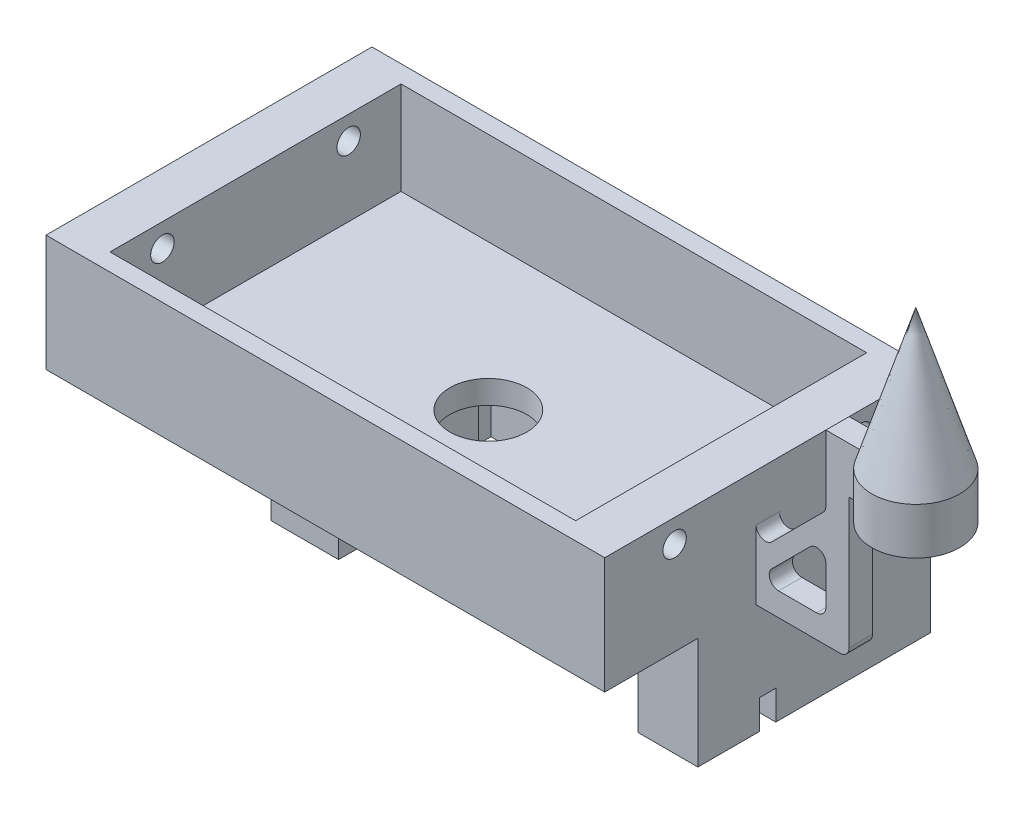
SolidWorks part; units mm, degrees
other "Markup1"
sketch "Sketch8" plane through (63.5, 15.875, 0) normal (0.0601, 0.2478, 0.9669) x (0.9981, -0.001, -0.0618)
ref_plane "Front Plane" through (0, 0, 0) normal (0, 0, 1) x (1, 0, 0)
ref_plane "Top Plane" through (0, 0, 0) normal (0, 1, 0) x (1, 0, 0)
ref_plane "Right Plane" through (0, 0, 0) normal (1, 0, 0) x (0, 0, -1)
sketch "Sketch1" plane through (0, 0, 0) normal (0, 1, 0) x (1, 0, 0)
  line L1 (0, 0) -> (63.5, 0)
  line L2 (0, 0) -> (0, 38.1)
  line L3 (0, 38.1) -> (63.5, 38.1)
  line L4 (63.5, 0) -> (63.5, 38.1)
  dimension "D1" = 38.1
  dimension "D2" = 63.5
extrude "Base" add sketch "Sketch1" along normal blind 3.175
sketch "Sketch3" plane through (0, 0, 0) normal (0, 1, 0) x (1, 0, 0)
  line L0 (0, 0) -> (63.5, 0) construction
  line L1 (0, 38.1) -> (-6.35, 38.1)
  line L2 (0, 38.1) -> (0, 0)
  line L3 (0, 0) -> (-6.35, 0)
  line L4 (-6.35, 38.1) -> (-6.35, 0)
  line L5 (63.5, 38.1) -> (69.85, 38.1)
  line L6 (63.5, 38.1) -> (63.5, 0)
  line L7 (63.5, 0) -> (69.85, 0)
  line L8 (69.85, 38.1) -> (69.85, 0)
  dimension "D1" = 6.35
extrude "Rod Holder" add sketch "Sketch3" along normal blind 15.875
sketch "Sketch4" plane through (69.85, 0, 0) normal (1, 0, 0) x (0, 0, -1)
  line L0 (0, 12.7) -> (38.1, 12.7) construction
  line L1 (0, 15.875) -> (0, 0) construction
  line L2 (38.1, 15.875) -> (38.1, 0) construction
  line L4 (38.1, 3.175) -> (0, 3.175) construction
  line L5 (0, 9.525) -> (38.1, 9.525) construction
  line L6 (11.595, 15.875) -> (11.595, 12.7) construction
  line L7 (0, 15.875) -> (38.1, 15.875) construction
  line L8 (11.595, 12.7) -> (11.595, 9.525) construction
  circle A0 centre (6.35, 12.7) radius 1.6
  circle A1 centre (31.75, 12.7) radius 1.6
  dimension "D1" = 3.2
  dimension "D3" = 6.35
  dimension "D2" = 6.35
  dimension "D4" = 6.35
extrude "Rod Hole" cut sketch "Sketch4" against normal through all
sketch "Sketch7" plane through (0, 3.175, 0) normal (0, 1, 0) x (1, 0, 0)
  line L0 (31.75, 38.1) -> (31.75, 0) construction
  line L1 (63.5, 38.1) -> (0, 38.1) construction
  line L2 (0, 0) -> (63.5, 0) construction
  circle A0 centre (31.75, 19.05) radius 5.25
  dimension "D1" = 10.5
extrude "GearPinHole_10.5mm" cut sketch "Sketch7" against normal through all
sketch "Sketch9" plane through (0, 0, 0) normal (0, -1, 0) x (1, 0, 0)
  line L1 (-6.35, 0) -> (69.85, 0)
  line L2 (-6.35, 0) -> (-6.35, 3.175)
  line L3 (-6.35, 3.175) -> (69.85, 3.175)
  line L4 (69.85, 0) -> (69.85, 3.175)
  line L5 (-6.35, -38.1) -> (69.85, -38.1)
  line L6 (-6.35, -38.1) -> (-6.35, -41.275)
  line L7 (-6.35, -41.275) -> (69.85, -41.275)
  line L8 (69.85, -38.1) -> (69.85, -41.275)
  dimension "D1" = 3.175
extrude "Boss-Extrude1" add sketch "Sketch9" against normal up to surface (15.875 mm away) up to face at (-3.175, 15.875, -19.05)
sketch "Sketch11" plane through (0, 0, 0) normal (0, -1, 0) x (1, 0, 0)
  line L0 (69.85, 3.175) -> (69.85, -41.275) construction
  line L1 (11.6546, -9.525) -> (19.85, -9.525)
  line L2 (11.6546, -9.525) -> (11.6546, -28.575)
  line L3 (11.6546, -28.575) -> (19.85, -28.575)
  line L4 (19.85, -9.525) -> (19.85, -28.575)
  line L5 (61.6546, -9.525) -> (69.85, -9.525)
  line L6 (61.6546, -9.525) -> (61.6546, -28.575)
  line L7 (61.6546, -28.575) -> (69.85, -28.575)
  line L8 (69.85, -9.525) -> (69.85, -28.575)
  point P14 (69.85, -19.05)
  point P15 (69.85, -19.05)
  dimension "D1" = 19.05
  dimension "D2" = 8.1954
extrude "Boss-Extrude2" add sketch "Sketch11" along normal blind 15.2
sketch "Sketch20" plane through (0, 0, 0) normal (0, -1, 0) x (1, 0, 0)
  line L1 (19.85, -9.525) -> (20.85, -9.525)
  line L2 (19.85, -9.525) -> (19.85, -28.575)
  line L3 (19.85, -28.575) -> (20.85, -28.575)
  line L4 (20.85, -9.525) -> (20.85, -28.575)
  dimension "D1" = 1
extrude "Boss-Extrude7" add sketch "Sketch20" along normal up to surface (15.2 mm away) up to face at (15.7523, -15.2, -19.05)
sketch "Sketch12" plane through (0, -15.2, 0) normal (0, -1, 0) x (1, 0, 0)
  line L2 (17.7523, -14.05) -> (20.85, -14.05) construction
  line L3 (20.85, -28.575) -> (20.85, -9.525) construction
  circle A0 centre (17.7523, -14.05) radius 1.5
  circle A1 centre (17.7523, -24.05) radius 1.5
  circle A2 centre (65.7523, -24.05) radius 1.5
  circle A3 centre (65.7523, -14.05) radius 1.5
  dimension "D1" = 3
  dimension "D2" = 3.0977
extrude "Cut-Extrude1" cut sketch "Sketch12" against normal blind 8.89
sketch "Sketch13" plane through (0, 0, 0) normal (0, -1, 0) x (1, 0, 0)
  line L1 (11.6546, -28.575) -> (16.7346, -28.575)
  line L2 (11.6546, -28.575) -> (11.6546, -41.275)
  line L4 (16.7346, -28.575) -> (16.7346, -34.417)
  line L5 (-6.35, -41.275) -> (69.85, -41.275) construction
  line L6 (69.85, -28.575) -> (64.77, -28.575)
  line L7 (69.85, -28.575) -> (69.85, -41.275)
  line L9 (64.77, -28.575) -> (64.77, -34.417)
  line L10 (16.7346, -34.417) -> (64.77, -34.417)
  line L12 (11.6546, -41.275) -> (69.85, -41.275)
  dimension "D1" = 5.08
  dimension "D2" = 6.858
extrude "Boss-Extrude3" add sketch "Sketch13" along normal up to surface (15.2 mm away) up to face at (17.7523, -15.2, -25.55)
sketch "Sketch14" plane through (0, 0, -41.275) normal (0, 0, -1) x (-1, 0, 0)
  line L0 (-11.6546, -15.2) -> (-11.6546, 0) construction
  line L2 (-40.7523, -15.2) -> (-40.7523, 15.875) construction
  line L5 (-11.6546, -15.2) -> (-69.85, -15.2) construction
  line L6 (-69.85, 15.875) -> (6.35, 15.875) construction
  line L7 (-62.7523, -7.6) -> (-18.7523, -7.6) construction
  circle A0 centre (-53.7523, -7.6) radius 1.75
  circle A1 centre (-27.7523, -7.6) radius 1.75
  point P3 (-11.6546, -7.6)
  point P18 (-40.7523, -7.6)
  dimension "D1" = 3.5
  dimension "D2" = 9
  dimension "D3" = 44
  dimension "D4" = 9
extrude "Cut-Extrude2" cut sketch "Sketch14" against normal up to surface (6.858 mm away) up to face at (40.7523, -7.6, -34.417)
sketch "Sketch15" plane through (0, 15.875, 0) normal (0, 1, 0) x (1, 0, 0)
  line L1 (0, 38.1) -> (63.5, 38.1)
  line L2 (0, 38.1) -> (0, 38.8938)
  line L3 (0, 38.8938) -> (63.5, 38.8938)
  line L4 (63.5, 38.1) -> (63.5, 38.8938)
  line L5 (0, 0) -> (63.5, 0)
  line L6 (0, 0) -> (0, -0.7938)
  line L7 (0, -0.7938) -> (63.5, -0.7938)
  line L8 (63.5, 0) -> (63.5, -0.7938)
  dimension "D1" = 0.7937
extrude "Cut-Extrude3" cut sketch "Sketch15" against normal up to surface (12.7 mm away) up to face at (31.75, 3.175, -13.8)
sketch "Sketch16" plane through (0, -15.2, 0) normal (0, -1, 0) x (1, 0, 0)
  line L1 (20.85, -20.15) -> (11.6546, -20.15)
  line L2 (20.85, -20.15) -> (20.85, -17.95)
  line L3 (20.85, -17.95) -> (11.6546, -17.95)
  line L4 (11.6546, -20.15) -> (11.6546, -17.95)
  line L5 (61.6546, -9.525) -> (61.6546, -28.575) construction
  line L6 (61.6546, -20.15) -> (69.85, -20.15)
  line L7 (61.6546, -20.15) -> (61.6546, -17.95)
  line L8 (61.6546, -17.95) -> (69.85, -17.95)
  line L9 (69.85, -20.15) -> (69.85, -17.95)
  line L10 (61.6546, -9.525) -> (61.6546, -28.575) construction
  line L11 (11.6546, -9.525) -> (11.6546, -41.275) construction
  line L12 (69.85, -41.275) -> (69.85, -9.525) construction
  line L13 (20.85, -28.575) -> (20.85, -9.525) construction
  point P4 (20.85, -19.05)
  point P13 (61.6546, -19.05)
  dimension "D1" = 2.2
extrude "Cut-Extrude4" cut sketch "Sketch16" against normal blind 4
sketch "Sketch17" plane through (0, 0, -41.275) normal (0, 0, -1) x (-1, 0, 0)
  line L1 (-69.85, 0) -> (-82.55, 0)
  line L2 (-69.85, 0) -> (-69.85, 3.175)
  line L3 (-69.85, 3.175) -> (-79.375, 3.175)
  line L6 (-82.55, 0) -> (-82.55, 25.4)
  line L7 (-82.55, 25.4) -> (-79.375, 25.4)
  line L8 (-79.375, 3.175) -> (-79.375, 25.4)
  dimension "D1" = 3.175
  dimension "D2" = 12.7
  dimension "D3" = 3.175
  dimension "D4" = 25.4
extrude "Boss-Extrude4" add sketch "Sketch17" along normal blind 1.5875 and the other way blind 1.5875 from offset 22.225 offset against normal yes
sketch "Sketch18" plane through (0, 25.4, 0) normal (0, 1, 0) x (1, 0, 0)
  line L6 (82.55, 17.4625) -> (82.55, 20.6375) construction
  line L7 (82.55, 20.6375) -> (84.2638, 20.6375)
  line L8 (82.55, 20.6375) -> (82.55, 17.4625)
  line L9 (82.55, 17.4625) -> (84.2638, 17.4625)
  circle A1 centre (90.05, 19.05) radius 5
  arc A2 (84.2638, 17.4625) -> (84.2638, 20.6375) centre (90.05, 19.05) ccw
  point P5 (82.55, 19.05)
  dimension "D1" = 10
  dimension "D2" = 12
  dimension "D3" = 7.5
extrude "Boss-Extrude5" add sketch "Sketch18" against normal blind 6.35
sketch "Sketch19" plane through (0, 0, -20.6375) normal (0, 0, -1) x (-1, 0, 0)
  line L0 (-79.375, 15.875) -> (-69.85, 6.35)
  line L1 (-79.375, 3.175) -> (-79.375, 25.4) construction
  line L2 (-69.85, 15.875) -> (-69.85, -15.2) construction
  line L3 (-69.85, 6.35) -> (-69.85, 3.175)
  line L4 (-69.85, 3.175) -> (-79.375, 12.7)
  line L5 (-79.375, 12.7) -> (-79.375, 15.875)
  line L6 (-69.85, 3.175) -> (-79.375, 3.175) construction
  line L7 (-69.85, 3.175) -> (-79.375, 3.175) construction
  dimension "D1" = 3.175
  dimension "D2" = 45
extrude "Boss-Extrude6" add sketch "Sketch19" against normal up to surface (3.175 mm away) up to face at (79.0097, 11.9062, -17.4625)
fillet "Fillet1" radius 1.27 5 edges at (69.85, 6.35, -19.05) (79.375, 15.875, -19.05) (79.375, 12.7, -19.05) (79.375, 3.175, -19.05) (82.55, 0, -19.05)
fillet "Fillet2" radius 1.27 1 edges at (69.85, 3.175, -19.05)
sketch "Sketch21" plane through (0, 25.4, 0) normal (0, 1, 0) x (1, 0, 0)
  circle A0 centre (90.05, 19.05) radius 5
extrude "Boss-Extrude8" add sketch "Sketch21" against normal up to surface (6.35 mm away) up to face at (85.05, 19.05, -19.05)
ref_plane "Plane1" through (0, 0, -19.05) normal (0, 0, 1) x (1, 0, 0)
sketch "Sketch22" plane through (0, 0, -19.05) normal (0, 0, 1) x (1, 0, 0)
  line L0 (90.05, 25.4) -> (90.05, 44.45)
  line L1 (95.05, 25.4) -> (85.05, 25.4) construction
  line L2 (90.05, 44.45) -> (96.05, 25.4)
  line L3 (90.05, 25.4) -> (96.05, 25.4)
  dimension "D1" = 19.05
revolve "Revolve1" add sketch "Sketch22" angle 360 about L0
